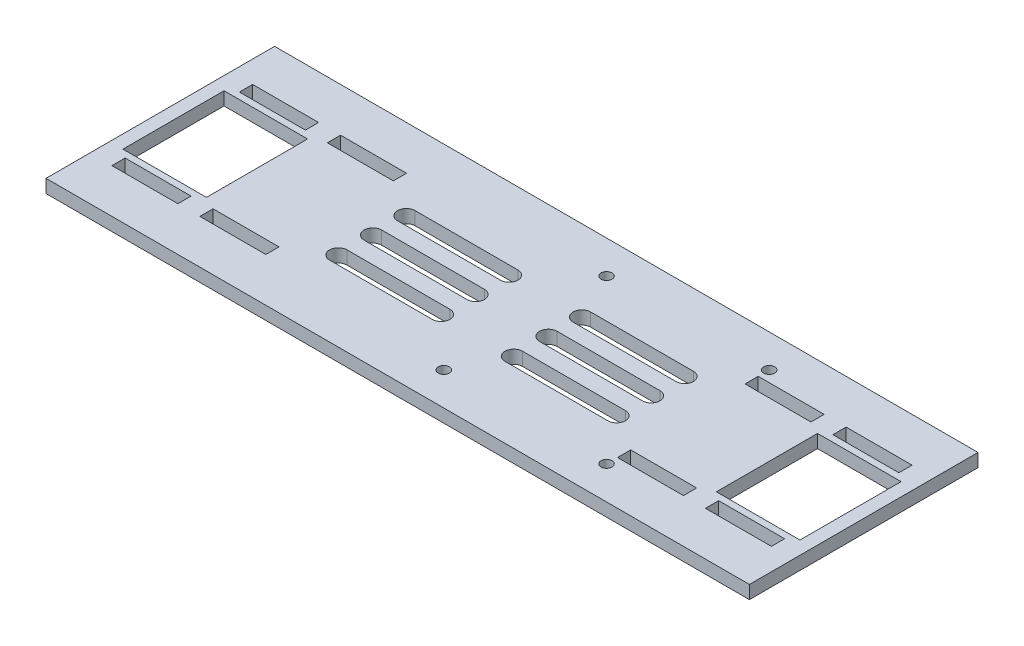
SolidWorks part; units mm, degrees
ref_plane "Front Plane" through (0, 0, 0) normal (0, 0, 1) x (1, 0, 0)
ref_plane "Top Plane" through (0, 0, 0) normal (0, 1, 0) x (1, 0, 0)
ref_plane "Right Plane" through (0, 0, 0) normal (1, 0, 0) x (0, 0, -1)
sketch "Sketch1" plane through (0, 0, 0) normal (0, 1, 0) x (1, 0, 0)
  line L0 (0, 0) -> (-15.3333, 0) construction
  line L1 (80, 26) -> (-80, 26)
  line L2 (80, 26) -> (80, -26)
  line L3 (80, -26) -> (-80, -26)
  line L4 (-80, 26) -> (-80, -26)
  line L5 (77, 7.2917) -> (77, -7.9583) construction
  line L6 (75, 16) -> (60, 16)
  line L7 (75, 16) -> (75, 13)
  line L8 (75, 13) -> (60, 13)
  line L9 (60, 16) -> (60, 13)
  line L10 (55, 16) -> (40, 16)
  line L11 (55, 16) -> (55, 13)
  line L12 (55, 13) -> (40, 13)
  line L13 (40, 16) -> (40, 13)
  line L14 (77, -11.5) -> (58, -11.5)
  line L15 (0, 0) -> (0, -4.375) construction
  line L16 (77, -11.5) -> (77, 11.5)
  line L17 (77, 11.5) -> (58, 11.5)
  line L18 (58, -11.5) -> (58, 11.5)
  line L19 (60, -16) -> (60, -13)
  line L20 (75, -13) -> (60, -13)
  line L21 (75, -16) -> (75, -13)
  line L22 (75, -16) -> (60, -16)
  line L23 (40, -16) -> (40, -13)
  line L24 (55, -13) -> (40, -13)
  line L25 (55, -16) -> (55, -13)
  line L26 (55, -16) -> (40, -16)
  line L27 (-77, 7.2917) -> (-77, -7.9583) construction
  line L28 (-55, -16) -> (-40, -16)
  line L29 (-55, -16) -> (-55, -13)
  line L30 (-55, -13) -> (-40, -13)
  line L31 (-40, -16) -> (-40, -13)
  line L32 (-75, -16) -> (-60, -16)
  line L33 (-75, -16) -> (-75, -13)
  line L34 (-75, -13) -> (-60, -13)
  line L35 (-60, -16) -> (-60, -13)
  line L36 (-58, -11.5) -> (-58, 11.5)
  line L37 (-77, 11.5) -> (-58, 11.5)
  line L38 (-77, -11.5) -> (-77, 11.5)
  line L39 (-77, -11.5) -> (-58, -11.5)
  line L40 (-40, 16) -> (-40, 13)
  line L41 (-55, 13) -> (-40, 13)
  line L42 (-55, 16) -> (-55, 13)
  line L43 (-55, 16) -> (-40, 16)
  line L44 (-60, 16) -> (-60, 13)
  line L45 (-75, 13) -> (-60, 13)
  line L46 (-75, 16) -> (-75, 13)
  line L47 (-75, 16) -> (-60, 16)
  dimension "D1" = 3
  dimension "D2" = 15
  dimension "D3" = 5
  dimension "D4" = 5
  dimension "D5" = 15
  dimension "D6" = 13
  dimension "D7" = 3
  dimension "D8" = 19
  dimension "D9" = 23
  dimension "D10" = 3
  dimension "D11" = 80
  dimension "D12" = 52
  dimension "D13" = 26
extrude "Boss-Extrude1" add sketch "Sketch1" along normal blind 3
sketch "Sketch2" plane through (0, 3, 0) normal (0, 1, 0) x (1, 0, 0)
  line L0 (-31.6585, 2) -> (-8.2664, 2)
  line L1 (31.6585, -9.8567) -> (8.2664, -9.8567)
  line L2 (31.6585, -5.8567) -> (8.2664, -5.8567)
  line L4 (-31.6585, -2) -> (-8.2664, -2)
  line L5 (-31.6585, 9.6208) -> (-8.2664, 9.6208)
  line L6 (-31.6585, 5.6208) -> (-8.2664, 5.6208)
  line L7 (31.6585, 5.6208) -> (8.2664, 5.6208)
  line L8 (31.6585, 9.6208) -> (8.2664, 9.6208)
  line L9 (-31.6585, -5.8567) -> (-8.2664, -5.8567)
  line L10 (31.6585, -2) -> (8.2664, -2)
  line L11 (31.6585, 2) -> (8.2664, 2)
  line L12 (-31.6585, -9.8567) -> (-8.2664, -9.8567)
  line L15 (0, 0) -> (-4.1634, 0) construction
  arc A0 (31.6585, -9.8567) -> (31.6585, -5.8567) centre (31.6585, -7.8567) ccw
  arc A1 (8.2664, -5.8567) -> (8.2664, -9.8567) centre (8.2664, -7.8567) ccw
  arc A2 (-8.2664, 2) -> (-8.2664, -2) centre (-8.2664, 0) cw
  arc A3 (-31.6585, -2) -> (-31.6585, 2) centre (-31.6585, 0) cw
  arc A4 (31.6585, 5.6208) -> (31.6585, 9.6208) centre (31.6585, 7.6208) ccw
  arc A5 (8.2664, 9.6208) -> (8.2664, 5.6208) centre (8.2664, 7.6208) ccw
  arc A6 (31.6585, -2) -> (31.6585, 2) centre (31.6585, 0) ccw
  arc A7 (8.2664, 2) -> (8.2664, -2) centre (8.2664, 0) ccw
  arc A8 (-8.2664, 9.6208) -> (-8.2664, 5.6208) centre (-8.2664, 7.6208) cw
  arc A9 (-31.6585, 5.6208) -> (-31.6585, 9.6208) centre (-31.6585, 7.6208) cw
  arc A10 (-8.2664, -5.8567) -> (-8.2664, -9.8567) centre (-8.2664, -7.8567) cw
  arc A11 (-31.6585, -9.8567) -> (-31.6585, -5.8567) centre (-31.6585, -7.8567) cw
extrude "Cut-Extrude1" cut sketch "Sketch2" against normal blind 3
sketch "Sketch3" plane through (0, 3, 0) normal (0, 1, 0) x (1, 0, 0)
  circle A0 centre (40, 18.5) radius 1.25
  circle A1 centre (40, -18.5) radius 1.25
  circle A2 centre (3, -18.5) radius 1.25
  circle A3 centre (3, 18.5) radius 1.25
  point P11 (0, 0)
  dimension "D1" = 18.5
  dimension "D2" = 3
  dimension "D3" = 2.5
  dimension "D4" = 2.5
  dimension "D5" = 2.5
  dimension "D6" = 2.5
extrude "Cut-Extrude2" cut sketch "Sketch3" against normal blind 10
